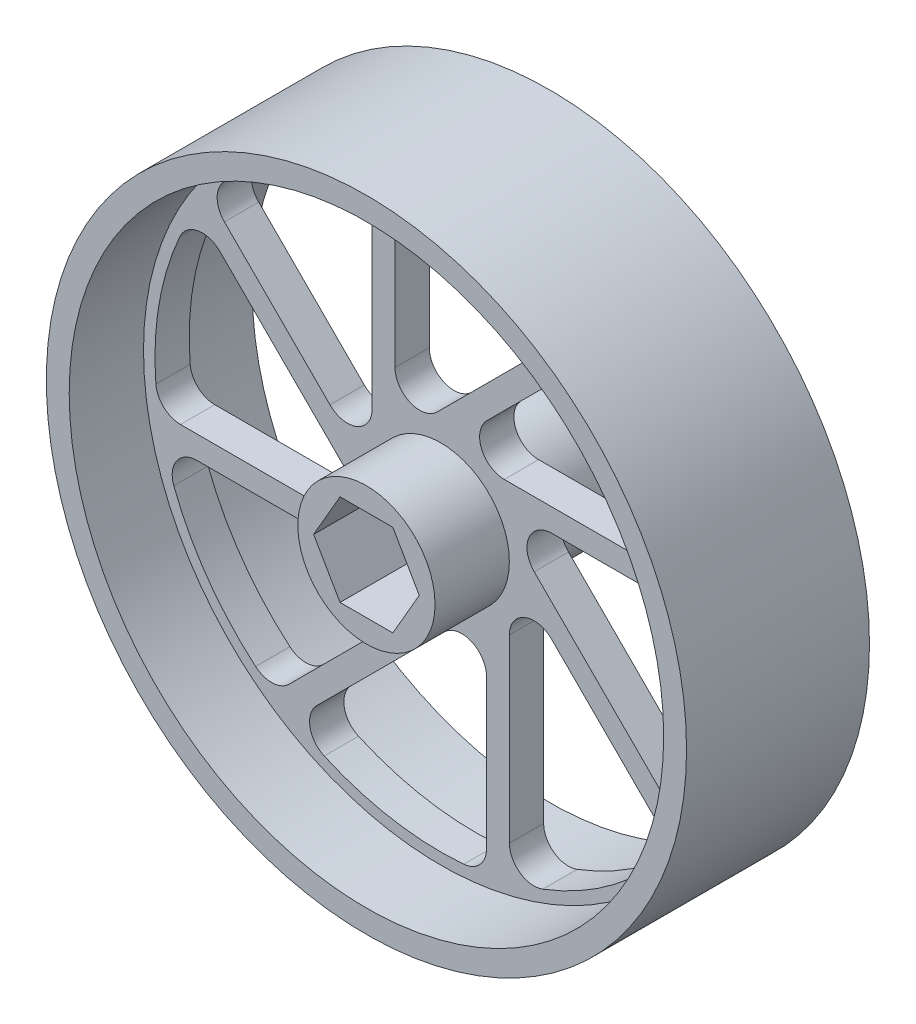
SolidWorks part; units mm, degrees
material "6061-T6 (SS)"
ref_plane "Front Plane" through (0, 0, 0) normal (0, 0, 1) x (1, 0, 0)
ref_plane "Top Plane" through (0, 0, 0) normal (0, 1, 0) x (1, 0, 0)
ref_plane "Right Plane" through (0, 0, 0) normal (1, 0, 0) x (0, 0, -1)
sketch "Sketch1" plane through (0, 0, 0) normal (0, 0, 1) x (1, 0, 0)
  line L1 (3.6662, -6.35) -> (7.3323, 0)
  line L2 (7.3323, 0) -> (3.6662, 6.35)
  line L3 (3.6662, 6.35) -> (-3.6662, 6.35)
  line L4 (-3.6662, 6.35) -> (-7.3323, 0)
  line L5 (-7.3323, 0) -> (-3.6662, -6.35)
  line L6 (-3.6662, -6.35) -> (3.6662, -6.35)
  circle A0 centre (0, 0) radius 44.45
  circle A1 centre (0, 0) radius 6.35 construction
  dimension "D1" = 88.9
  dimension "D2" = 12.7
extrude "Boss-Extrude1" add sketch "Sketch1" along normal mid plane 25.4
sketch "Sketch2" plane through (0, 0, 12.7) normal (0, 0, 1) x (1, 0, 0)
  circle A0 centre (0, 0) radius 9.525
  circle A1 centre (0, 0) radius 41.275
  circle A2 centre (0, 0) radius 44.45 construction
  dimension "D1" = 3.175
  dimension "D2" = 19.05
extrude "Cut-Extrude1" cut sketch "Sketch2" against normal through all
sketch "Sketch4" plane through (0, 0, 0) normal (0, 0, 1) x (1, 0, 0)
  line L0 (-9.525, 0) -> (-9.525, 40.1609)
  line L1 (-6.35, 7.0995) -> (-6.35, 40.7836)
  circle A2 centre (0, 0) radius 9.525 construction
  circle A3 centre (0, 0) radius 41.275 construction
  arc A4 (-6.35, 40.7836) -> (-9.525, 40.1609) centre (0, 0) ccw
  arc A5 (-6.35, 7.0995) -> (-9.525, 0) centre (0, 0) ccw
  dimension "D1" = 3.175
extrude "Boss-Extrude2" add sketch "Sketch4" along normal mid plane 4.7625
sketch "Sketch5" plane through (0, 0, 2.3813) normal (0, 0, 1) x (1, 0, 0)
  circle A0 centre (0, 0) radius 41.275
  circle A1 centre (0, 0) radius 39.6875
  circle A2 centre (0, 0) radius 41.275 construction
  circle A3 centre (0, 0) radius 44.45 construction
  dimension "D1" = 4.7625
extrude "Boss-Extrude3" add sketch "Sketch5" against normal up to surface (4.7625 mm away) up to face at (-8.1284, 22.1035, -2.3812)
fillet "Fillet1" radius 3.429 2 edges at (-9.525, 38.5275, 0) (-6.35, 39.1762, 0)
pattern_circular "CirPattern1" count 8 over 360 about axis through (0, 0, 12.7) along (0, 0, -1) of "Boss-Extrude2", "Fillet1"
fillet "Fillet2" radius 3.429 8 edges at (0.5447, 9.525, 0) (-6.35, 7.1204, 0) (-9.525, 0.5447, 0) (-7.1204, -6.35, 0) (-0.5447, -9.525, 0) (6.35, -7.1204, 0) (9.525, -0.5447, 0) (7.1204, 6.35, 0)
